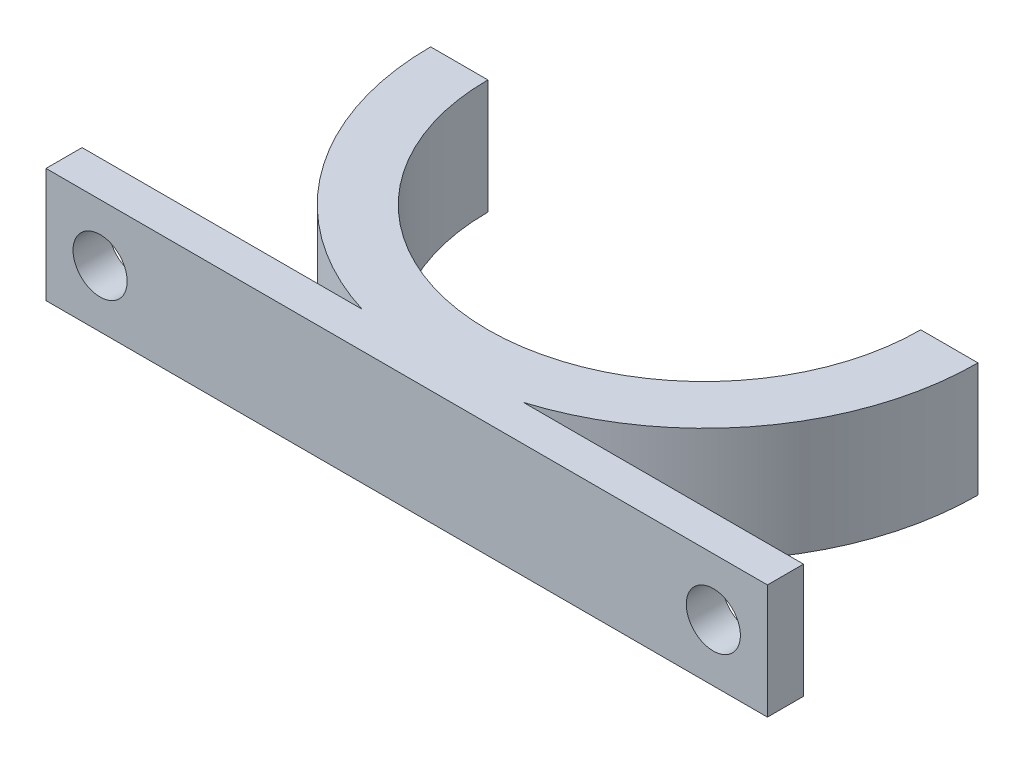
SolidWorks part; units mm, degrees
ref_plane "Front Plane" through (0, 0, 0) normal (0, 0, 1) x (1, 0, 0)
ref_plane "Top Plane" through (0, 0, 0) normal (0, 1, 0) x (1, 0, 0)
ref_plane "Right Plane" through (0, 0, 0) normal (1, 0, 0) x (0, 0, -1)
sketch "Sketch1" plane through (0, 0, 0) normal (0, 1, 0) x (1, 0, 0)
  line L0 (0, 0) -> (20, 0)
  line L4 (-12, 16.5) -> (-15.175, 16.5)
  line L5 (12, 16.5) -> (15.175, 16.5)
  line L6 (0, 0) -> (-20, 0)
  line L7 (-14.8391, 19.675) -> (14.8391, 19.675) construction
  line L8 (-12, 16.5) -> (12, 16.5) construction
  line L9 (-20, 0) -> (-20, 2)
  line L10 (-20, 2) -> (-4.4756, 2)
  line L11 (20, 2) -> (20, 0)
  line L12 (4.4756, 2) -> (20, 2)
  arc A0 (-12, 16.5) -> (12, 16.5) centre (0, 16.5) ccw
  arc A1 (-15.175, 16.5) -> (-4.4756, 2) centre (0, 16.5) ccw
  arc A2 (-14.8391, 19.675) -> (14.8391, 19.675) centre (0, 16.5) ccw construction
  arc A3 (4.4756, 2) -> (15.175, 16.5) centre (0, 16.5) ccw
  arc A4 (-12, 16.5) -> (12, 16.5) centre (0, 16.5) ccw construction
  point P4 (0, 0)
  point P16 (-4.782, 16.5)
  dimension "D2" = 24
  dimension "D3" = 0
  dimension "D1" = 16.5
  dimension "D5" = 20
  dimension "D6" = 20
  dimension "D7" = 2
  dimension "D4" = 3.175
extrude "Boss-Extrude1" add sketch "Sketch1" along normal blind 6.35
sketch "Sketch2" plane through (0, 0, -2) normal (0, 0, -1) x (-1, 0, 0)
  line L0 (-20, 0) -> (-4.4756, 0) construction
  line L1 (4.4756, 0) -> (20, 0) construction
  line L2 (20, 6.35) -> (20, 0) construction
  line L3 (-20, 6.35) -> (-20, 0) construction
  circle A0 centre (-17, 3.175) radius 1.5
  circle A1 centre (17, 3.175) radius 1.5
  point P0 (17, 3.175)
  point P1 (-17, 3.175)
  dimension "D5" = 3
  dimension "D6" = 3
  dimension "D1" = 3.175
  dimension "D2" = 3.175
  dimension "D3" = 3
  dimension "D4" = 3
extrude "Cut-Extrude1" cut sketch "Sketch2" against normal blind 6.35
